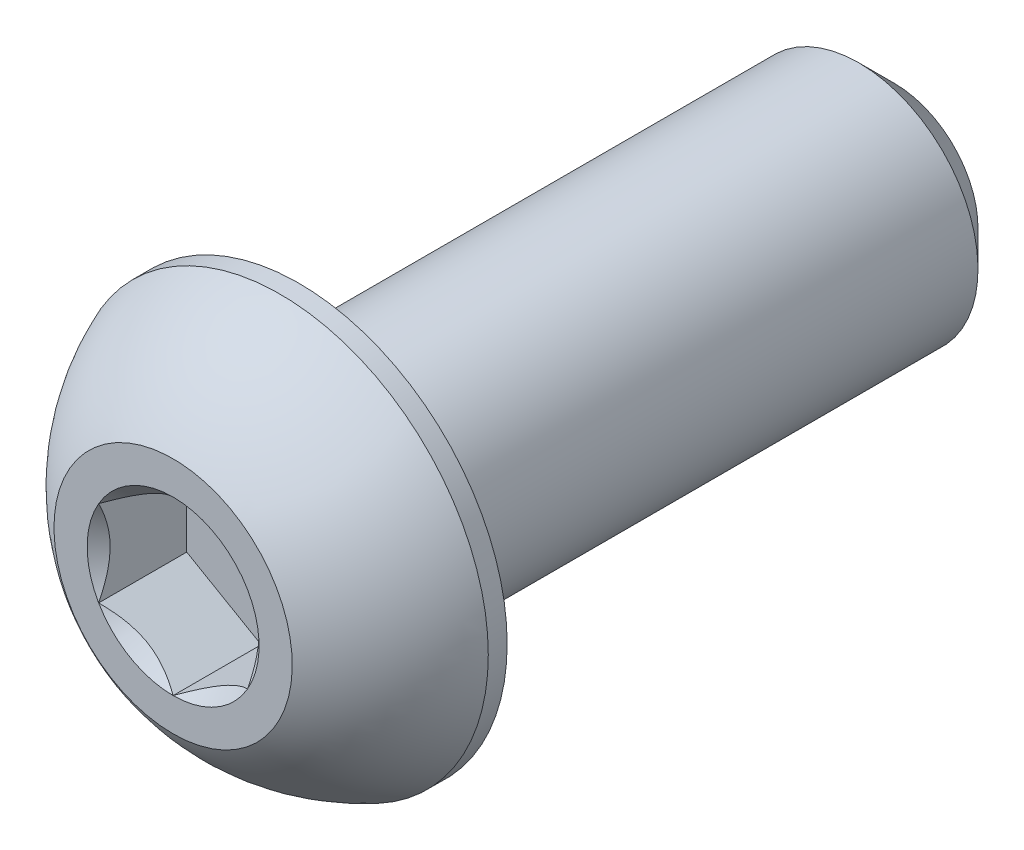
SolidWorks part; units mm, degrees
material "Alloy Steel"
ref_plane "Front" through (0, 0, 0) normal (0, 0, 1) x (1, 0, 0)
ref_plane "Top" through (0, 0, 0) normal (0, 1, 0) x (1, 0, 0)
ref_plane "Right" through (0, 0, 0) normal (1, 0, 0) x (0, 0, -1)
sketch "Sketch1" plane through (0, 0, 0) normal (1, 0, 0) x (0, 0, -1)
  line L2 (3.3528, 3.175) -> (19.2278, 3.175)
  line L3 (19.2278, 3.175) -> (19.2278, 0)
  line L4 (19.2278, 0) -> (3.3528, 0)
  line L6 (2.8499, 5.5499) -> (3.3528, 5.5499) construction
  line L7 (19.2278, 3.175) -> (19.2278, -3.175) construction
  line L8 (0, 0) -> (3.3528, 0) construction
  line L9 (3.3528, 5.5499) -> (3.3528, -5.5499) construction
  line L11 (3.3528, 3.175) -> (3.3528, 0)
  line L13 (0, 1.9844) -> (0, -1.9844) construction
  line L14 (0, 1.9844) -> (0, 3.175) construction
  arc A3 (0, 3.175) -> (2.8499, 5.5499) centre (5.0603, 0) cw construction
  dimension "D1" = 0.5029
revolve "Revolve1" add sketch "Sketch1" angle 360 mid plane about L4
sketch "Sketch3" plane through (0, 0, -19.2278) normal (0, 0, -1) x (-1, 0, 0)
  circle A0 centre (0, 0) radius 3.175
curve "Helix/Spiral1" pitch 1.27 height 17.145 turns 13.5
sketch "Sketch2" plane through (0, 0, 0) normal (1, 0, 0) x (0, 0, -1)
  line L0 (19.2278, 3.175) -> (20.339, 3.175)
  line L1 (20.339, 3.175) -> (19.8628, 2.3501)
  line L2 (19.8628, 2.3501) -> (19.704, 2.3501)
  line L3 (19.704, 2.3501) -> (19.2278, 3.175)
  line L4 (19.4659, 2.7626) -> (20.1009, 2.7626) construction
  dimension "D1" = 60
  dimension "D2" = 0.1588
  dimension "D3" = 0.635
chamfer "Chamfer1" distance 0.9525 angle 45 1 edges at (0, 3.175, -19.2278)
sweep "Cut-Sweep1" [suppressed] cut profiles "Sketch2" path "Helix/Spiral1"
sketch "Sketch7" plane through (0, 0, 0) normal (1, 0, 0) x (0, 0, -1)
  line L6 (2.8499, 5.5499) -> (3.3528, 5.5499) construction
  line L8 (0, 0) -> (3.3528, 0) construction
  line L11 (3.3528, 5.5499) -> (3.3528, -5.5499) construction
  line L12 (2.8499, 5.5499) -> (3.3528, 5.5499)
  line L13 (0, 0) -> (3.3528, 0)
  line L14 (0, 1.9844) -> (0, -1.9844) construction
  line L15 (3.3528, 5.5499) -> (3.3528, 0)
  line L16 (0, 3.175) -> (0, 0)
  arc A2 (2.8499, 5.5499) -> (0, 3.175) centre (5.0603, 0) ccw construction
  arc A3 (2.8499, 5.5499) -> (0, 3.175) centre (5.0603, 0) ccw
revolve "Revolve2" add sketch "Sketch7" angle 360 mid plane about L13
sketch "Sketch5" plane through (0, 0, 0) normal (0, 0, 1) x (1, 0, 0)
  line L1 (1.9844, -1.1457) -> (1.9844, 1.1457)
  line L2 (1.9844, 1.1457) -> (0, 2.2914)
  line L3 (0, 2.2914) -> (-1.9844, 1.1457)
  line L4 (-1.9844, 1.1457) -> (-1.9844, -1.1457)
  line L5 (-1.9844, -1.1457) -> (0, -2.2914)
  line L6 (0, -2.2914) -> (1.9844, -1.1457)
  circle A0 centre (0, 0) radius 1.9844 construction
extrude "Cut-Extrude2" cut sketch "Sketch5" against normal blind 2.347
sketch "Sketch6" plane through (0, 0, 0) normal (0, 0, 1) x (1, 0, 0)
  circle A0 centre (0, 0) radius 2.2914
extrude "Cut-Extrude3" cut sketch "Sketch6" against normal blind 2.347 draft 45
sketch "Sketch9" [suppressed] plane through (0, 0, -3.3528) normal (0, 0, 1) x (1, 0, 0)
  circle A2 centre (0, 0) radius 3.175
extrude "Boss-Extrude2" [suppressed] add sketch "Sketch9" against normal offset from surface (12.7 mm away) 22.225
sketch "Sketch10" plane through (0, 0, 0) normal (1, 0, 0) x (0, 0, -1)
  line L0 (19.2278, 3.175) -> (19.2278, -3.175) construction
  point P0 (17.3228, -3.175)
  dimension "D1" = 1.905
equation "\"D3@Helix/Spiral1\" = \"Lg@Sketch1\" + \"D4@Helix/Spiral1\""
equation "\"D2@Sketch2\" = \"D4@Helix/Spiral1\" * .125"
equation "\"D3@Sketch2\" = \"D4@Helix/Spiral1\" * .5"
equation "\"D1@Chamfer1\" = \"D4@Helix/Spiral1\" * .75"
equation "\"D1@Cut-Extrude2\" = \"Head Ht@Sketch1\" * .7"
equation "\"D1@Sketch1\" = \"Head Ht@Sketch1\" * .15"
equation "\"D1@Sketch10\" = \"D4@Helix/Spiral1\" * 1.5"
equation "\"D1@Cut-Extrude3\" = \"D1@Cut-Extrude2\""
